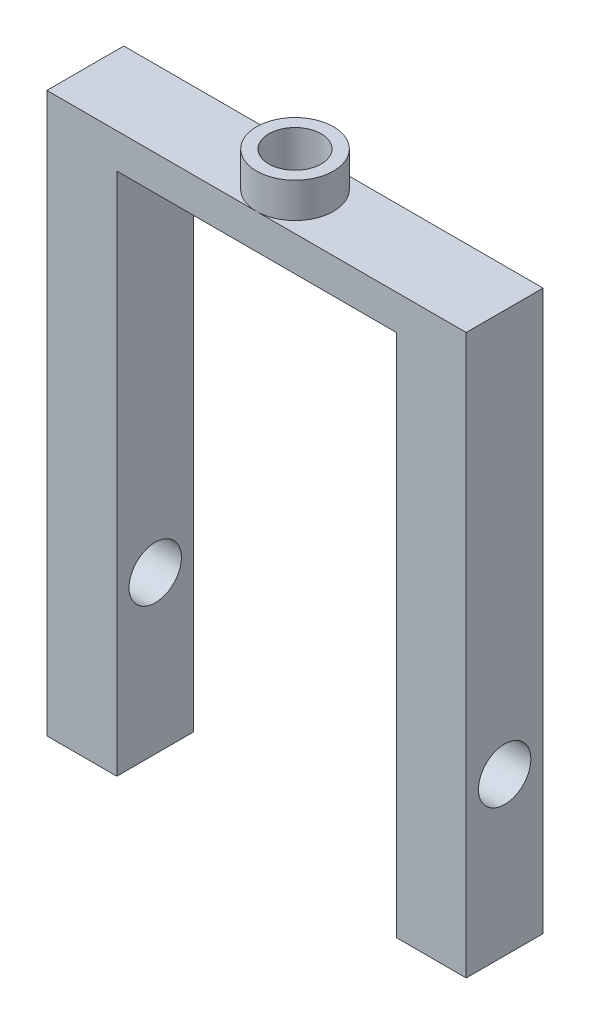
SolidWorks part; units mm, degrees
ref_plane "Front Plane" through (0, 0, 0) normal (0, 0, 1) x (1, 0, 0)
ref_plane "Top Plane" through (0, 0, 0) normal (0, 1, 0) x (1, 0, 0)
ref_plane "Right Plane" through (0, 0, 0) normal (1, 0, 0) x (0, 0, -1)
sketch "Sketch1" plane through (0, 0, 0) normal (0, 1, 0) x (1, 0, 0)
  circle A0 centre (0, 0) radius 6.985
  dimension "D1" = 13.97
extrude "Boss-Extrude1" add sketch "Sketch1" against normal blind 6.35
sketch "Sketch3" plane through (0, 0, 0) normal (0, 1, 0) x (1, 0, 0)
  circle A0 centre (0, 0) radius 4.7625
  circle A1 centre (0, 0) radius 6.985 construction
  dimension "D1" = 9.525
extrude "Cut-Extrude1" cut sketch "Sketch3" against normal blind 63.5
sketch "Sketch4" plane through (0, 0, 0) normal (0, 1, 0) x (1, 0, 0)
  line L0 (6.985, 0) -> (8.8102, 0) construction
  circle A0 centre (0, 0) radius 6.985 construction
  dimension "D1" = 1.8252
sketch "Sketch5" plane through (0, -6.35, 0) normal (0, -1, 0) x (-1, 0, 0)
  line L1 (38.1, -6.985) -> (-38.1, -6.985)
  line L2 (38.1, -6.985) -> (38.1, 6.985)
  line L3 (38.1, 6.985) -> (-38.1, 6.985)
  line L4 (-38.1, -6.985) -> (-38.1, 6.985)
  line L5 (38.1, -6.985) -> (-38.1, 6.985) construction
  line L6 (38.1, 6.985) -> (-38.1, -6.985) construction
  circle A0 centre (0, 0) radius 4.7625 construction
  point P0 (0, 0)
  dimension "D1" = 76.2
  dimension "D2" = 13.97
extrude "Boss-Extrude2" add sketch "Sketch5" along normal blind 101.6
sketch "Sketch6" plane through (0, 0, -6.985) normal (0, 0, -1) x (-1, 0, 0)
  line L0 (0, -6.35) -> (-38.1, -6.35) construction
  line L1 (25.4, -12.7) -> (-25.4, -12.7)
  line L2 (25.4, -12.7) -> (25.4, -107.95)
  line L3 (25.4, -107.95) -> (-25.4, -107.95)
  line L4 (-25.4, -12.7) -> (-25.4, -107.95)
  line L5 (25.4, -12.7) -> (-25.4, -107.95) construction
  line L6 (25.4, -107.95) -> (-25.4, -12.7) construction
  line L7 (38.1, -107.95) -> (38.1, -6.35) construction
  line L8 (38.1, -107.95) -> (-38.1, -107.95) construction
  point P0 (0, -64.4831)
  point P14 (0, -60.325)
  dimension "D1" = 50.8
  dimension "D3" = 6.35
  dimension "D4" = 38.1
extrude "Cut-Extrude2" cut sketch "Sketch6" against normal through all
sketch "Sketch7" plane through (0, 0, 0) normal (0, 1, 0) x (1, 0, 0)
  circle A0 centre (0, 0) radius 4.7625
  dimension "D1" = 9.525
extrude "Cut-Extrude3" cut sketch "Sketch7" against normal through all
sketch "Sketch8" plane through (25.4, 0, 0) normal (-1, 0, 0) x (0, 0, 1)
  line L0 (6.985, -12.7) -> (-6.985, -12.7) construction
  line L1 (-6.985, -12.7) -> (-6.985, -107.95) construction
  circle A0 centre (0, -79.375) radius 4.7625
  dimension "D1" = 9.525
  dimension "D2" = 66.675
  dimension "D3" = 6.985
extrude "Cut-Extrude4" cut sketch "Sketch8" against normal blind 19.05 and the other way through all
